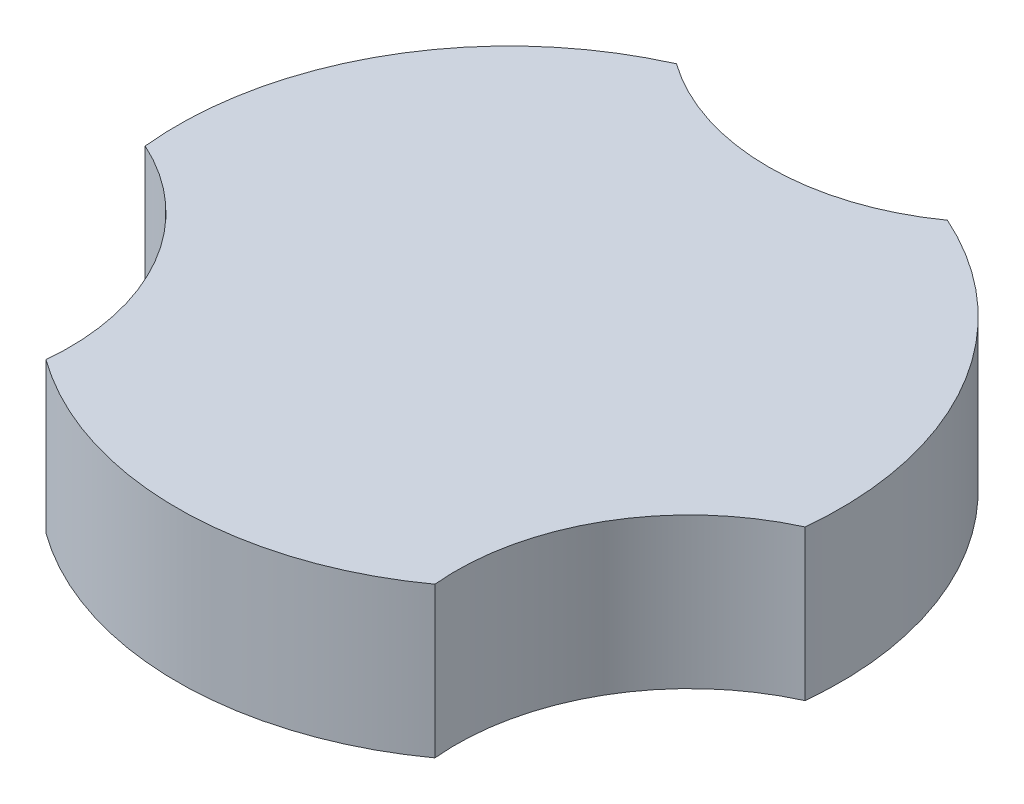
SolidWorks part; units mm, degrees
ref_plane "Front Plane" through (0, 0, 0) normal (0, 0, 1) x (1, 0, 0)
ref_plane "Top Plane" through (0, 0, 0) normal (0, 1, 0) x (1, 0, 0)
ref_plane "Right Plane" through (0, 0, 0) normal (1, 0, 0) x (0, 0, -1)
sketch "Lens Sketch" plane through (0, 0, 0) normal (0, 1, 0) x (1, 0, 0)
  circle A0 centre (0, 0) radius 14
  circle A2 centre (0, 20.8) radius 9.85
  circle A3 centre (18.0133, -10.4) radius 9.85
  circle A4 centre (-18.0133, -10.4) radius 9.85
  point P7 (0, 0)
  point P8 (0, 0)
  point P12 (0, 0)
  dimension "D1" = 28
  dimension "D3" = 19.7
  dimension "D4" = 20.8
  dimension "D5" = 3
extrude "Lens" add sketch "Lens Sketch" along normal blind 6.35 contours A4 A0 A3 A2 region at (0, 0, 0)
